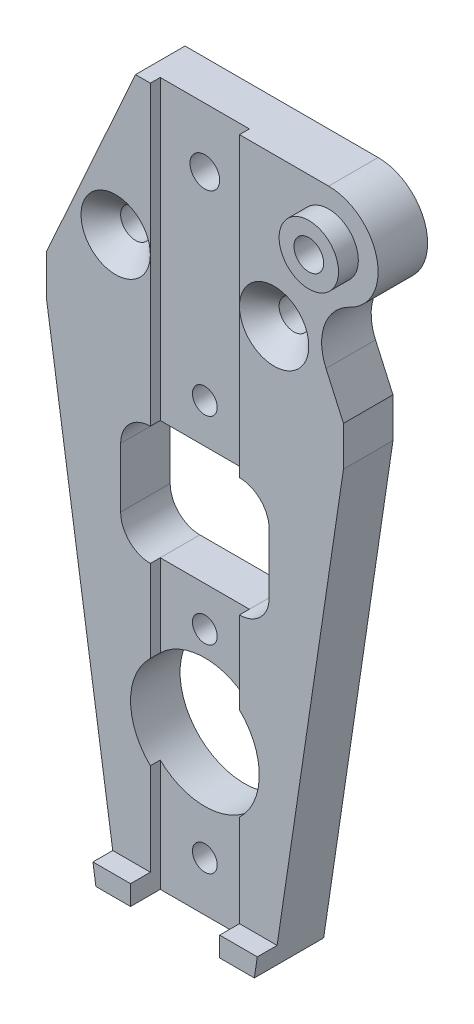
SolidWorks part; units mm, degrees
material "6061 合金"
ref_plane "前视基准面" through (0, 0, 0) normal (0, 0, 1) x (1, 0, 0)
ref_plane "上视基准面" through (0, 0, 0) normal (0, 1, 0) x (1, 0, 0)
ref_plane "右视基准面" through (0, 0, 0) normal (1, 0, 0) x (0, 0, -1)
sketch "草图1" plane through (0, 0, 0) normal (0, 0, 1) x (1, 0, 0)
  line L0 (0, 0) -> (0, 77.5694) construction
  line L1 (6, 55) -> (-6, 55)
  line L2 (-7.5, 13) -> (7.5, 13)
  line L3 (-7.5, 13) -> (-7.5, 25)
  line L4 (-7.5, 25) -> (7.5, 25)
  line L5 (7.5, 13) -> (7.5, 25)
  line L6 (-7.5, 13) -> (7.5, 25) construction
  line L7 (-7.5, 25) -> (7.5, 13) construction
  line L8 (-6, 55) -> (-15, 35)
  line L10 (-15, 35) -> (15, 35) construction
  line L11 (-4.5, 55) -> (-4.5, 39.2144) construction
  line L13 (6, 55) -> (15, 35)
  line L15 (-8, -16) -> (8, -16)
  line L16 (0, 0) -> (0, -39.4346) construction
  line L18 (-15, 35) -> (-15, 31)
  line L19 (-15, 31) -> (-8, -16)
  line L20 (15, 31) -> (8, -16)
  line L21 (15, 35) -> (15, 31)
  circle A0 centre (0, 0) radius 6.5
  circle A2 centre (0, 49) radius 1.5
  circle A3 centre (-8, 40) radius 1.5
  circle A4 centre (0, 29) radius 1.25 construction
  circle A5 centre (0, 9) radius 1.25 construction
  circle A6 centre (0, -11) radius 1.25 construction
  circle A7 centre (8, 40) radius 1.5
  point P4 (0, 19)
  point P28 (0, -16)
  point P33 (0, 55)
  dimension "D1" = 13
  dimension "D5" = 35
  dimension "D8" = 3
  dimension "D9" = 14
  dimension "D10" = 3
  dimension "D11" = 16
  dimension "D13" = 2.5
  dimension "D14" = 20
  dimension "D15" = 2.5
  dimension "D16" = 20
  dimension "D17" = 2.5
  dimension "D18" = 20
  dimension "D20" = 5
  dimension "D21" = 5
  dimension "D2" = 15
  dimension "D3" = 12
  dimension "D4" = 13
  dimension "D6" = 6
  dimension "D7" = 20
  dimension "D12" = 4.5
  dimension "D19" = 30
  dimension "D22" = 8
  dimension "D23" = 4
extrude "凸台-拉伸1" add sketch "草图1" along normal blind 5
hole_wizard "M3 螺纹孔1" positions "草图7" profile "草图8" tap size "M3" standard "GB" end condition through all
sketch "草图7" plane through (0, 0, 5) normal (0, 0, 1) x (1, 0, 0)
  point P0 (0, 29)
  point P3 (0, 9)
  point P6 (0, -11)
sketch "草图8" plane through (0, 29, 5) normal (1, 0, 0) x (0, -1, 0)
  line L0 (0, 0) -> (0, 5)
  line L1 (0, 5) -> (1.25, 5)
  line L2 (1.25, 5) -> (1.25, 0)
  line L5 (1.25, 0) -> (0, 0)
  line L11 (0, -6.35) -> (0, 107.95) construction
  dimension "通孔螺纹孔钻头直径" = 2.5
  dimension "通孔螺纹孔钻头深度" = 5
cosmetic thread "孔螺纹线1" parameters "D2"=3
cosmetic thread "孔螺纹线2" parameters "D2"=3
cosmetic thread "孔螺纹线3" parameters "D2"=3
sketch "草图2" plane through (0, 0, 5) normal (0, 0, 1) x (1, 0, 0)
  line L0 (0, -18.9795) -> (0, 64.8101) construction
  line L1 (4.5, -18.9795) -> (4.5, 64.8101)
  line L2 (-4.5, -18.9795) -> (-4.5, 64.8101)
  line L3 (-4.5, 64.8101) -> (4.5, 64.8101)
  line L4 (-4.5, -18.9795) -> (4.5, -18.9795)
  dimension "D1" = 4.5
  dimension "D2" = 4.5
extrude "切除-拉伸1" cut sketch "草图2" against normal blind 1
fillet "圆角1" radius 3 4 edges at (7.5, 13, 2.5) (-7.5, 13, 2.5) (-7.5, 25, 2.5) (7.5, 25, 2.5)
sketch "草图4" plane through (0, 0, 5) normal (0, 0, 1) x (1, 0, 0)
  line L0 (-8, -16) -> (-4.5, -16) construction
  line L1 (-15, 31) -> (-8, -16) construction
  line L2 (-8, -16) -> (-4.5, -16)
  line L3 (-8.2979, -14) -> (-8, -16)
  line L4 (0, 0) -> (0, -29.8573) construction
  line L5 (-4.5, -16) -> (-4.5, -14)
  line L6 (-4.5, -4.6904) -> (-4.5, -16) construction
  line L7 (-4.5, -14) -> (-8.2979, -14)
  line L8 (4.5, -14) -> (8.2979, -14)
  line L9 (4.5, -16) -> (4.5, -14)
  line L10 (8, -16) -> (4.5, -16)
  line L11 (8.2979, -14) -> (8, -16)
  dimension "D1" = 2
extrude "凸台-拉伸2" add sketch "草图4" along normal blind 2
chamfer "倒角1" distance 2 angle 45 2 edges at (6.5, 40, 5) (-6.5, 40, 5)
sketch "草图5" plane through (0, 0, 5) normal (0, 0, 1) x (1, 0, 0)
  line L0 (6, 55) -> (13.5, 55)
  line L1 (15, 35) -> (6, 55) construction
  line L2 (9.7258, 46.7205) -> (6, 55)
  circle A0 centre (13.5, 50) radius 1.5
  circle A1 centre (0, 49) radius 1.5 construction
  arc A2 (9.7258, 46.7205) -> (13.5, 55) centre (13.5, 50) ccw
  dimension "D1" = 3
  dimension "D2" = 13.5
  dimension "D3" = 5
extrude "凸台-拉伸4" add sketch "草图5" against normal up to surface (5 mm away) up to face at (1.25, 29, 0)
fillet "圆角2" radius 5 1 edges at (9.7258, 46.7205, 2.5)
sketch "草图6" plane through (0, 0, 5) normal (0, 0, 1) x (1, 0, 0)
  circle A2 centre (13.5, 50) radius 1.5
  circle A3 centre (13.5, 50) radius 1.5 construction
  circle A4 centre (13.5, 50) radius 3
  dimension "D1" = 6
extrude "凸台-拉伸5" add sketch "草图6" along normal blind 2
